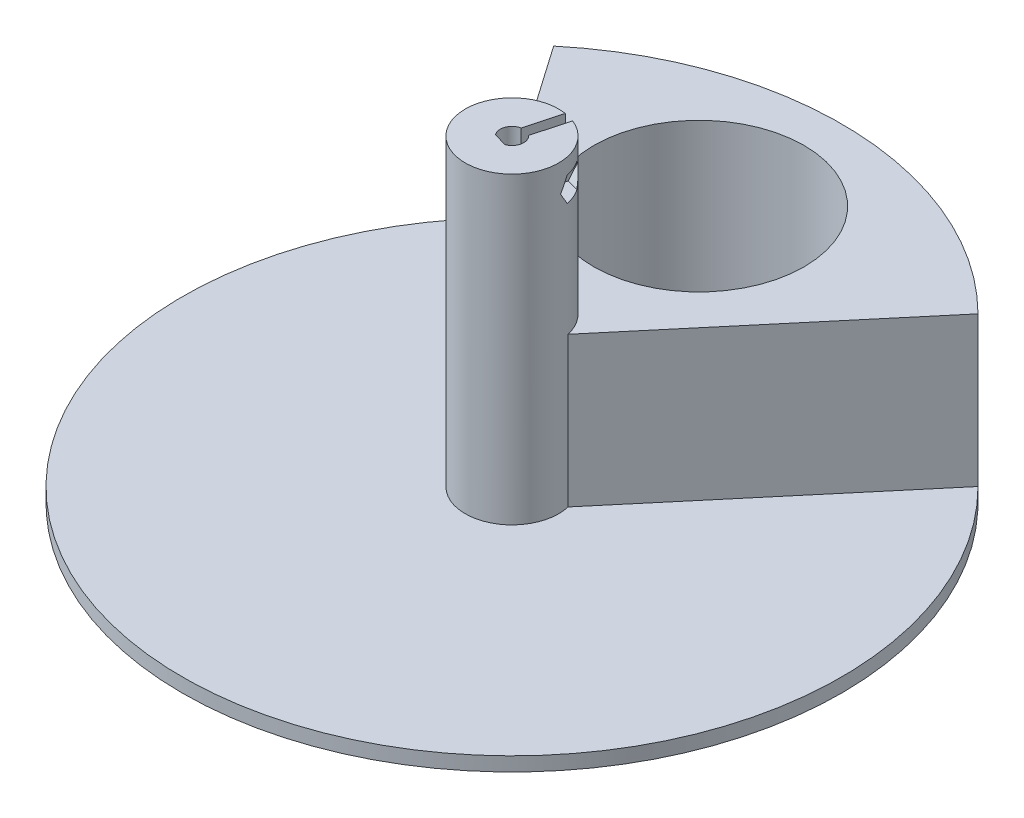
SolidWorks part; units mm, degrees
ref_plane "Front" through (0, 0, 0) normal (0, 0, 1) x (1, 0, 0)
ref_plane "Top" through (0, 0, 0) normal (0, 1, 0) x (1, 0, 0)
ref_plane "Right" through (0, 0, 0) normal (1, 0, 0) x (0, 0, -1)
sketch "Sketch3" plane through (0, 0, 0) normal (0, 1, 0) x (1, 0, 0)
  circle A0 centre (0, 0) radius 70.5
  dimension "D1" = 141
extrude "Boss-Extrude2" add sketch "Sketch3" along normal blind 38
sketch "Sketch4" plane through (0, 38, 0) normal (0, 1, 0) x (1, 0, 0)
  line L0 (1.4451, -2.04) -> (-1.4451, -2.04)
  circle A1 centre (0, 40) radius 22.5
  arc A2 (1.4451, -2.04) -> (-1.4451, -2.04) centre (0, 0) ccw
  dimension "D1" = 45
  dimension "D4" = 2.5
  dimension "D2" = 40
  dimension "D5" = 2.04
  dimension "D6" = 2.04
extrude "Cut-Extrude1" cut sketch "Sketch4" against normal blind 89
sketch "Sketch6" plane through (0, 38, 0) normal (0, 1, 0) x (1, 0, 0)
  line L0 (-45.1962, 54.1068) -> (-0.5571, -9.9845)
  line L1 (-0.5571, -9.9845) -> (49.8038, 49.8982)
  arc A0 (-45.1962, 54.1068) -> (49.8038, 49.8982) centre (0, 0) ccw
  circle A1 centre (0, 0) radius 70.5 construction
  dimension "D1" = 10
  dimension "D2" = 95
  dimension "D3" = 6
extrude "Cut-Extrude2" cut sketch "Sketch6" against normal blind 35
ref_axis "Axis1" through (0, 0, 0) along (0, 1, 0)
sketch "Sketch8" plane through (0, 3, 0) normal (0, 1, 0) x (1, 0, 0)
  circle A0 centre (0, 0) radius 10
  dimension "D1" = 20
extrude "Boss-Extrude3" add sketch "Sketch8" along normal blind 65 contours A0
sketch "Sketch10" plane through (0, 68, 0) normal (0, 1, 0) x (1, 0, 0)
  line L0 (-1.9999, -1.5167) -> (0.8265, -2.37)
  arc A0 (-1.9999, -1.5167) -> (0.8265, -2.37) centre (0, 0) cw
  dimension "D1" = 2.51
  dimension "D2" = 2.03
extrude "Cut-Extrude4" cut sketch "Sketch10" against normal blind 30
sketch "Sketch11" plane through (0, 38, 0) normal (0, 1, 0) x (1, 0, 0)
  line L0 (49.8038, 49.8982) -> (9.7411, 2.2608) construction
  line L1 (-45.1962, 54.1068) -> (-9.5583, 2.9392)
  line L2 (49.8038, 49.8982) -> (9.7411, 2.2608)
  arc A1 (-9.5583, 2.9392) -> (9.7411, 2.2608) centre (0, 0) cw
  arc A2 (49.8038, 49.8982) -> (-45.1962, 54.1068) centre (0, 0) ccw
  arc A3 (49.8038, 49.8982) -> (-45.1962, 54.1068) centre (0, 0) ccw construction
extrude "Cut-Extrude5" cut sketch "Sketch11" against normal blind 3
sketch "Sketch12" plane through (0, 3, 0) normal (0, -1, 0) x (1, 0, 0)
  line L0 (-1.4451, 2.04) -> (1.4451, 2.04) construction
  line L1 (-1.4451, 2.04) -> (1.4451, 2.04)
  arc A0 (-1.4451, 2.04) -> (1.4451, 2.04) centre (0, 0) ccw
extrude "Cut-Extrude6" cut sketch "Sketch12" against normal blind 10
sketch "Sketch13" plane through (0, 68, 0) normal (0, 1, 0) x (1, 0, 0)
  line L0 (-0.4965, 2.4604) -> (1.6746, 1.8697)
  line L1 (-0.4965, 2.4604) -> (1.6036, 10.1798)
  line L2 (1.6746, 1.8697) -> (3.7747, 9.5892)
  line L3 (1.6036, 10.1798) -> (3.7747, 9.5892)
  arc A0 (0.8265, -2.37) -> (-1.9999, -1.5167) centre (0, 0) ccw construction
  dimension "D1" = 8
  dimension "D2" = 2.25
extrude "Cut-Extrude7" cut sketch "Sketch13" against normal blind 20
sketch "Sketch14" plane through (-1.0855, 0, -0.2953) normal (0.9649, 0, 0.2625) x (0.2625, 0, -0.9649)
  line L0 (9.9365, 68) -> (2.2438, 68) construction
  circle A0 centre (6.0577, 62) radius 1.55
  dimension "D1" = 3.1
  dimension "D2" = 6
extrude "Cut-Extrude9" cut sketch "Sketch14" against normal blind 12 and the other way blind 12 contours A0
ref_plane "Plane1" through (10.4936, 0, 2.8549) normal (0.9649, 0, 0.2625) x (0.2625, 0, -0.9649)
sketch "Sketch15" plane through (10.4936, 0, 2.8549) normal (0.9649, 0, 0.2625) x (0.2625, 0, -0.9649)
  line L1 (9.1077, 62) -> (7.5827, 64.6414)
  line L2 (7.5827, 64.6414) -> (4.5327, 64.6414)
  line L3 (4.5327, 64.6414) -> (3.0077, 62)
  line L4 (3.0077, 62) -> (4.5327, 59.3586)
  line L5 (4.5327, 59.3586) -> (7.5827, 59.3586)
  line L6 (7.5827, 59.3586) -> (9.1077, 62)
  circle A0 centre (6.0577, 62) radius 2.6414 construction
  dimension "D1" = 6.1
extrude "Cut-Extrude10" cut sketch "Sketch15" against normal blind 7
ref_plane "Plane2" through (-10.4936, 0, -2.8549) normal (-0.9649, 0, -0.2625) x (-0.2625, 0, 0.9649)
sketch "Sketch16" plane through (-10.4936, 0, -2.8549) normal (-0.9649, 0, -0.2625) x (-0.2625, 0, 0.9649)
  circle A0 centre (-6.0577, 62) radius 3.05
  dimension "D1" = 6.1
extrude "Cut-Extrude11" cut sketch "Sketch16" against normal blind 7
